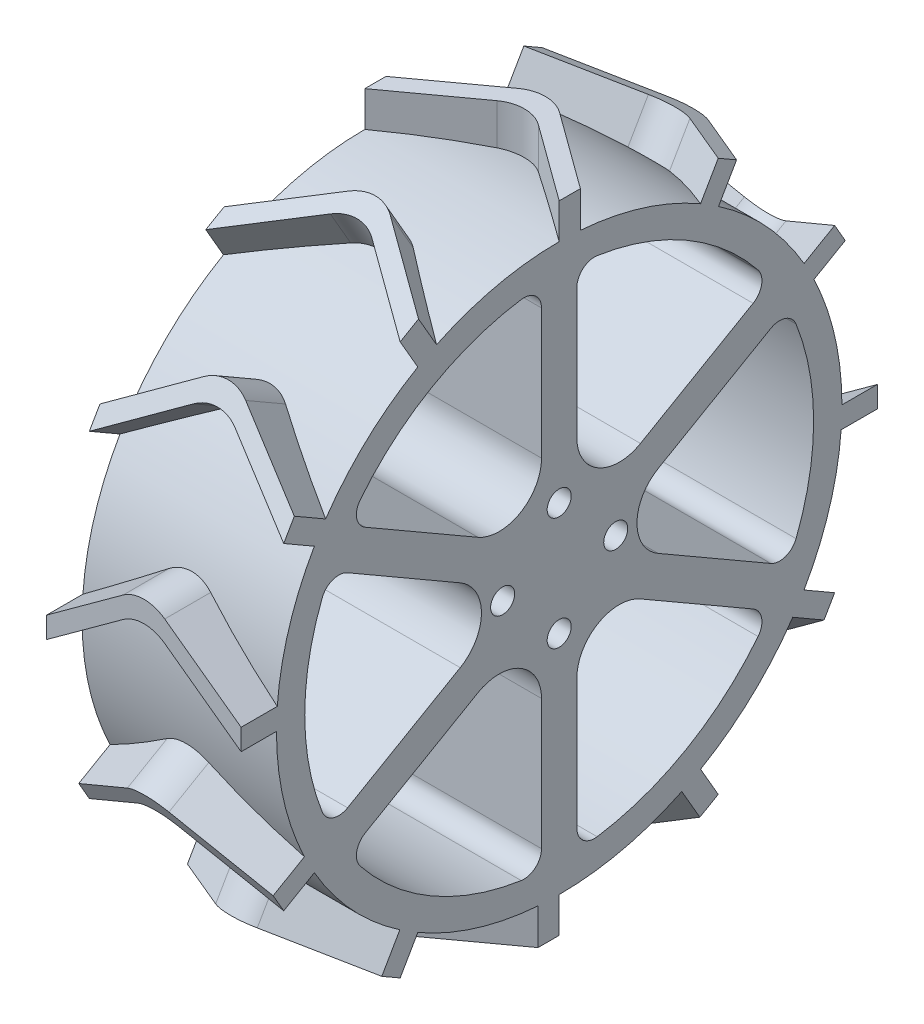
SolidWorks part; units mm, degrees
material "PLA 15%"
ref_plane "Front Plane" through (0, 0, 0) normal (0, 0, 1) x (1, 0, 0)
ref_plane "Top Plane" through (0, 0, 0) normal (0, 1, 0) x (1, 0, 0)
ref_plane "Right Plane" through (0, 0, 0) normal (1, 0, 0) x (0, 0, -1)
sketch "Sketch2" plane through (0, 0, 0) normal (1, 0, 0) x (0, 0, -1)
  circle A2 centre (0, 0) radius 40
  dimension "D1" = 80
extrude "Boss-Extrude1" add sketch "Sketch2" along normal blind 27.5
sketch "Sketch4" plane through (0, 0, 0) normal (0, 1, 0) x (1, 0, 0)
  line L8 (0, 0) -> (27.5, 0) construction
  line L9 (27.5, -40) -> (27.5, 40) construction
  line L10 (0, 0) -> (10.8091, 7.8612)
  line L11 (16.6909, 7.8612) -> (27.5, 0)
  line L12 (27.5, 0) -> (27.5, 3)
  line L13 (27.5, 3) -> (16.6909, 10.8612)
  line L14 (10.8091, 10.8612) -> (0, 3)
  line L15 (0, 40) -> (0, -40) construction
  line L16 (0, 3) -> (0, 0)
  arc A0 (16.6909, 10.8612) -> (10.8091, 10.8612) centre (13.75, 6.8175) ccw
  arc A1 (10.8091, 7.8612) -> (16.6909, 7.8612) centre (13.75, 3.8175) cw
  point P4 (13.75, 0)
  point P18 (13.75, 13)
  point P21 (13.75, 10)
  dimension "D3" = 5
  dimension "D1" = 3
  dimension "D2" = 3
  dimension "D4" = 10
extrude "Boss-Extrude2" add sketch "Sketch4" along normal blind 45
pattern_circular "CirPattern2" count 12 over 360 about axis through (27.5, 0, 0) along (-1, 0, 0) of "Boss-Extrude2"
sketch "Sketch5" plane through (0, 0, 0) normal (-1, 0, 0) x (0, 0, 1)
  line L0 (0, 0) -> (0, 40) construction
  line L1 (0, 0) -> (34.641, 20) construction
  line L6 (2.5, 33.1248) -> (2.5, 4.3301)
  line L8 (27.4369, 18.7274) -> (2.5, 4.3301)
  circle A0 centre (0, 0) radius 40 construction
  arc A2 (5.3731, 35.5968) -> (28.1411, 22.4517) centre (0, 0) cw
  arc A6 (28.1411, 22.4517) -> (27.4369, 18.7274) centre (26.1869, 20.8925) cw
  arc A7 (5.3731, 35.5968) -> (2.5, 33.1248) centre (5, 33.1248) ccw
  circle A10 centre (0, 0) radius 40 construction
  point P11 (0, 35.9131)
  point P22 (2.5, 35.9131)
  dimension "D1" = 2.5
  dimension "D2" = 4
  dimension "D8" = 2.5
  dimension "D7" = 2.5
  dimension "D9" = 60
extrude "Cut-Extrude3" cut sketch "Sketch5" against normal up to next
fillet "Fillet1" radius 6 1 edges at (13.75, 4.3301, 2.5)
pattern_circular "CirPattern3" count 6 over 360 about axis through (0, 0, 0) along (1, 0, 0) of "Cut-Extrude3", "Fillet1"
sketch "Sketch6" plane through (0, 0, 0) normal (-1, 0, 0) x (0, 0, 1)
  circle A0 centre (0, 8) radius 1.7
  circle A1 centre (8, 0) radius 1.7
  circle A2 centre (0, -8) radius 1.7
  circle A3 centre (-8, 0) radius 1.7
  point P0 (0, 0)
  point P4 (0, 0)
  point P6 (9.8133, -1.0126)
  point P7 (0, 0)
  point P13 (0, 0)
  dimension "D1" = 3.4
  dimension "D2" = 8
  dimension "D3" = 4
extrude "Cut-Extrude4" cut sketch "Sketch6" against normal up to next
sketch "Sketch7" plane through (0, 0, 0) normal (0, 1, 0) x (1, 0, 0)
